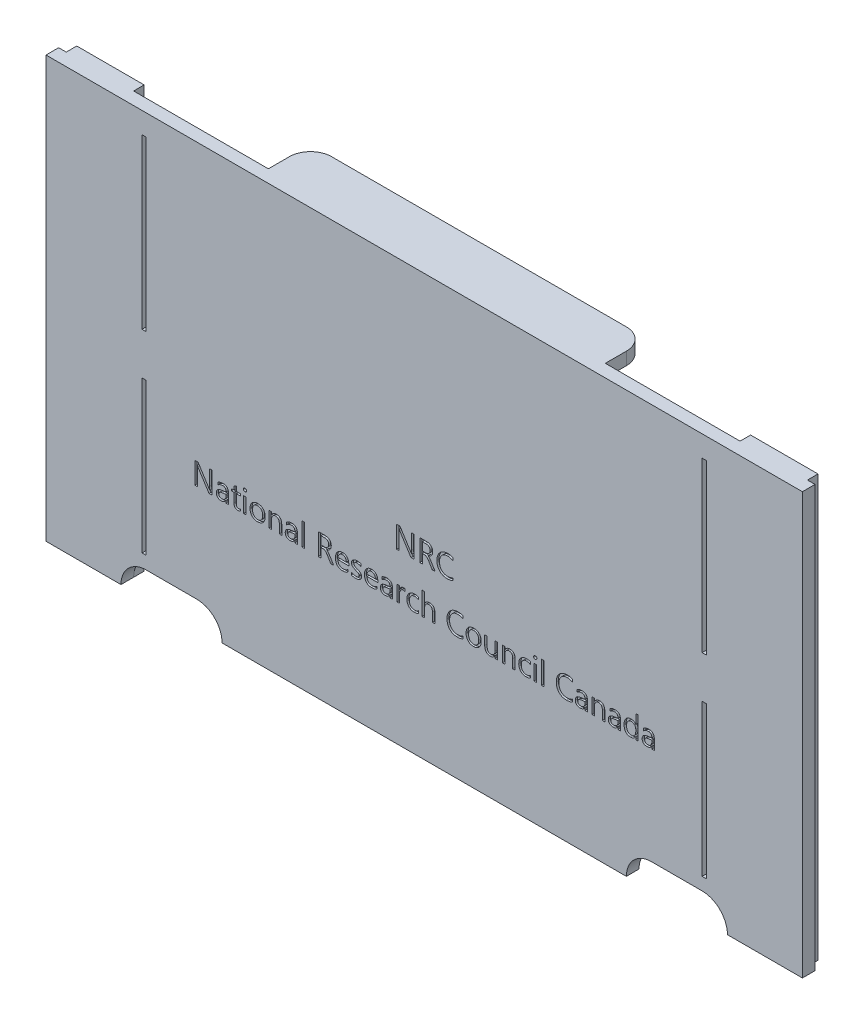
SolidWorks part; units mm, degrees
ref_plane "Front Plane" through (0, 0, 0) normal (0, 0, 1) x (1, 0, 0)
ref_plane "Top Plane" through (0, 0, 0) normal (0, 1, 0) x (1, 0, 0)
ref_plane "Right Plane" through (0, 0, 0) normal (1, 0, 0) x (0, 0, -1)
sketch "Sketch1" plane through (0, 0, 0) normal (0, 0, 1) x (1, 0, 0)
  line L1 (90, -50) -> (-90, -50)
  line L2 (90, -50) -> (90, 50)
  line L3 (90, 50) -> (-90, 50)
  line L4 (-90, -50) -> (-90, 50)
  line L5 (90, -50) -> (-90, 50) construction
  line L6 (90, 50) -> (-90, -50) construction
  point P0 (0, 0)
  dimension "D1" = 180
  dimension "D2" = 100
extrude "Boss-Extrude1" add sketch "Sketch1" along normal blind 3
sketch "Sketch2" plane through (0, 0, 0) normal (0, 0, -1) x (-1, 0, 0)
  line L0 (-80, 63.7201) -> (-80, -49936.2799) construction
  line L1 (80, 64.2305) -> (80, -49935.7695) construction
  dimension "D1" = 80
  dimension "D2" = 80
sketch "Sketch3" plane through (0, 0, 0) normal (0, 0, -1) x (-1, 0, 0)
  line L0 (-80, 200063.7201) -> (-80, -249936.2799) construction
  line L1 (-72, -50) -> (-88, -50)
  line L2 (-72, -50) -> (-72, 50)
  line L3 (-72, 50) -> (-88, 50)
  line L4 (-88, -50) -> (-88, 50)
  line L5 (-72, -50) -> (-88, 50) construction
  line L6 (-72, 50) -> (-88, -50) construction
  line L7 (-90, 50) -> (90, 50) construction
  line L8 (80, 200064.2305) -> (80, -249935.7695) construction
  line L9 (88, -50) -> (72, -50)
  line L10 (88, -50) -> (88, 50)
  line L11 (88, 50) -> (72, 50)
  line L12 (72, -50) -> (72, 50)
  line L13 (88, -50) -> (72, 50) construction
  line L14 (88, 50) -> (72, -50) construction
  point P0 (-80, 0)
  point P9 (80, 0)
  dimension "D1" = 16
  dimension "D2" = 16
extrude "Boss-Extrude2" add sketch "Sketch3" along normal blind 2.5
sketch "Sketch4" plane through (0, 0, -2.5) normal (0, 0, -1) x (-1, 0, 0)
  line L0 (-80, 200063.7201) -> (-80, -249936.2799) construction
  line L1 (-86.1, 47.75) -> (-73.9, 47.75)
  line L2 (-86.1, 47.75) -> (-86.1, 42.25)
  line L3 (-86.1, 42.25) -> (-73.9, 42.25)
  line L4 (-73.9, 47.75) -> (-73.9, 42.25)
  line L5 (-86.1, 47.75) -> (-73.9, 42.25) construction
  line L6 (-86.1, 42.25) -> (-73.9, 47.75) construction
  line L7 (-72, 50) -> (-88, 50) construction
  point P0 (-80, 45)
  dimension "D1" = 12.2
  dimension "D2" = 5
  dimension "D3" = 5.5
extrude "Cut-Extrude1" cut sketch "Sketch4" against normal blind 1.5
mirror "Mirror1" about plane through (0, 0, 0) normal (1, 0, 0) of "Cut-Extrude1"
pattern_linear "LPattern1" count 4 spacing 30 along (0, -1, 0) of "Mirror1"
sketch "Sketch5" plane through (0, 0, 3) normal (0, 0, 1) x (1, 0, 0)
  line L0 (-90, -10) -> (90, -10) construction
  line L1 (-90, 50) -> (-90, -50) construction
  line L2 (90, -50) -> (90, 50) construction
  text T0 "NRC\r\nNational Research Council Canada" font "Yu Gothic UI" height in points 20
  dimension "D1" = 10
extrude "Cut-Extrude2" cut sketch "Sketch5" against normal blind 0.5
sketch "Sketch6" plane through (0, 50, 0) normal (0, 1, 0) x (1, 0, 0)
  line L0 (90, -3) -> (-90, -3) construction
  line L1 (-90, 0) -> (-89.8, 0)
  line L2 (-90, 0) -> (-90, -3)
  line L3 (-90, -3) -> (-89.8, -3)
  line L4 (-89.8, 0) -> (-89.8, -3)
  line L6 (90, 0) -> (89.8, 0)
  line L7 (90, 0) -> (90, -3)
  line L8 (90, -3) -> (89.8, -3)
  line L9 (89.8, 0) -> (89.8, -3)
  dimension "D1" = 0.2
  dimension "D2" = 0.2
extrude "Cut-Extrude3" cut sketch "Sketch6" against normal through all both and the other way through all
sketch "Sketch8" plane through (0, 0, 3) normal (0, 0, 1) x (1, 0, 0)
  line L0 (-60, 10.6106) -> (-60, -49989.3894) construction
  line L1 (60, 23.1735) -> (60, -49976.8265) construction
  dimension "D1" = 60
  dimension "D2" = 60
sketch "Sketch10" plane through (0, 0, 3) normal (0, 0, 1) x (1, 0, 0)
  line L0 (-66, -50) -> (-54, -50) construction
  line L1 (-60, 200010.6106) -> (-60, -249989.3894) construction
  line L2 (-89.8, -50) -> (89.8, -50) construction
  line L3 (-66, -44) -> (-54, -44)
  line L4 (-66, -56) -> (-54, -56)
  arc A0 (-66, -44) -> (-66, -56) centre (-66, -50) ccw
  arc A1 (-54, -56) -> (-54, -44) centre (-54, -50) ccw
  point P6 (-60, -50)
  dimension "D1" = 12
  dimension "D2" = 12
extrude "Cut-Extrude4" cut sketch "Sketch10" against normal through all both and the other way through all
mirror "Mirror3" about plane through (0, 0, 0) normal (1, 0, 0) of "Cut-Extrude4"
sketch "Sketch11" plane through (0, 0, -2.5) normal (0, 0, -1) x (-1, 0, 0)
  line L0 (-73.9, 12.25) -> (-80, -7.75)
  line L1 (-80, 200063.7201) -> (-80, -249936.2799) construction
  line L2 (-80, -7.75) -> (-86.1, 12.25)
  line L3 (-86.1, 12.25) -> (-73.9, 12.25)
  dimension "D1" = 20
extrude "Cut-Extrude5" cut sketch "Sketch11" against normal blind 1.5
pattern_linear "LPattern2" count 2 spacing 30 along (0, 1, 0) count 2 spacing 30 along (0, -1, 0) of "Cut-Extrude5" pattern seed only yes
mirror "Mirror4" about plane through (0, 0, 0) normal (1, 0, 0) of "LPattern2"
sketch "Sketch12" plane through (0, 0, -2.5) normal (0, 0, -1) x (-1, 0, 0)
  line L0 (-88, -50) -> (-72, -50) construction
  line L1 (-86.1, -47.75) -> (-73.9, -47.75)
  line L2 (-86.1, -47.75) -> (-86.1, -50)
  line L3 (-86.1, -50) -> (-73.9, -50)
  line L4 (-73.9, -47.75) -> (-73.9, -50)
extrude "Cut-Extrude6" cut sketch "Sketch12" against normal blind 1.5
mirror "Mirror5" about plane through (0, 0, 0) normal (1, 0, 0) of "Cut-Extrude6"
sketch "Sketch13" plane through (0, 0, 0) normal (0, 0, -1) x (-1, 0, 0)
  line L0 (-72, -50) -> (-72, 50) construction
  line L1 (-67, 45) -> (-66, 45)
  line L2 (-67, 45) -> (-67, 5)
  line L3 (-67, 5) -> (-66, 5)
  line L4 (-66, 45) -> (-66, 5)
  line L5 (-72, -50) -> (-72, 50) construction
  line L8 (-67, -5) -> (-66, -5)
  line L9 (-67, -5) -> (-67, -41)
  line L10 (-67, -41) -> (-66, -41)
  line L11 (-66, -5) -> (-66, -41)
  dimension "D1" = 5
  dimension "D2" = 1
  dimension "D3" = 40
  dimension "D4" = 5
  dimension "D5" = 5
  dimension "D6" = 36
  dimension "D7" = 5
  dimension "D8" = 1
extrude "Cut-Extrude7" cut sketch "Sketch13" against normal blind 10
mirror "Mirror7" about plane through (0, 0, 0) normal (1, 0, 0) of "Cut-Extrude7"
sketch "Sketch15" plane through (0, 0, 0) normal (0, 0, -1) x (-1, 0, 0)
  line L0 (-72, 50) -> (72, 50) construction
  line L1 (-40, 50) -> (40, 50)
  line L2 (-40, 50) -> (-40, 47)
  line L3 (-40, 47) -> (40, 47)
  line L4 (40, 50) -> (40, 47)
  dimension "D1" = 80
  dimension "D2" = 40
  dimension "D3" = 3
extrude "Boss-Extrude4" add sketch "Sketch15" along normal blind 10
fillet "Fillet2" radius 5 2 edges at (-40, 48.5, -10) (40, 48.5, -10)
fillet "Fillet3" radius 3 1 edges at (0, 47, 0)
